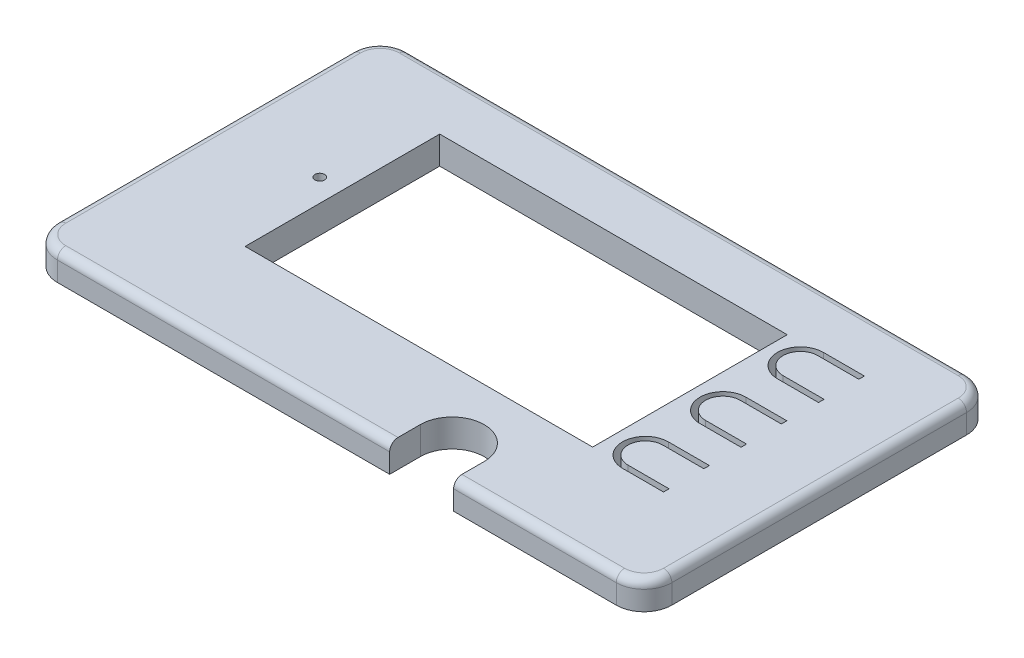
SolidWorks part; units mm, degrees
ref_plane "Front Plane" through (0, 0, 0) normal (0, 0, 1) x (1, 0, 0)
ref_plane "Top Plane" through (0, 0, 0) normal (0, 1, 0) x (1, 0, 0)
ref_plane "Right Plane" through (0, 0, 0) normal (1, 0, 0) x (0, 0, -1)
sketch "Sketch1" plane through (0, 0, 0) normal (0, 1, 0) x (1, 0, 0)
  line L1 (-28.067, -16.002) -> (28.067, -16.002)
  line L2 (-28.067, -16.002) -> (-28.067, 16.002)
  line L3 (-28.067, 16.002) -> (28.067, 16.002)
  line L4 (28.067, -16.002) -> (28.067, 16.002)
  line L5 (-28.067, -16.002) -> (28.067, 16.002) construction
  line L6 (-28.067, 16.002) -> (28.067, -16.002) construction
  point P0 (0, 0)
  dimension "D1" = 56.134
  dimension "D2" = 32.004
extrude "Boss-Extrude1" add sketch "Sketch1" along normal blind 2.54
sketch "Sketch2" plane through (0, 2.54, 0) normal (0, 1, 0) x (1, 0, 0)
  line L0 (28.067, -16.002) -> (28.067, 16.002) construction
  line L1 (14.478, -7.112) -> (-17.272, -7.112)
  line L2 (14.478, -7.112) -> (14.478, 10.668)
  line L3 (14.478, 10.668) -> (-17.272, 10.668)
  line L4 (-17.272, -7.112) -> (-17.272, 10.668)
  line L5 (14.478, -7.112) -> (-17.272, 10.668) construction
  line L6 (14.478, 10.668) -> (-17.272, -7.112) construction
  line L9 (28.067, 16.002) -> (-28.067, 16.002) construction
  point P0 (-1.397, 1.778)
  point P6 (1.7092, -3.8207)
  dimension "D1" = 13.589
  dimension "D2" = 17.78
  dimension "D3" = 31.75
  dimension "D4" = 5.334
extrude "Cut-Extrude1" cut sketch "Sketch2" against normal up to surface (2.54 mm away) up to face at (0, 0, 0)
fillet "Fillet1" radius 2.54 4 edges at (-28.067, 1.27, -16.002) (28.067, 1.27, -16.002) (28.067, 1.27, 16.002) (-28.067, 1.27, 16.002)
sketch "Sketch3" plane through (0, 0, 0) normal (0, -1, 0) x (1, 0, 0)
  line L1 (28.067, 13.462) -> (28.067, -13.462) construction
  line L2 (25.527, -16.002) -> (-25.527, -16.002) construction
  circle A0 centre (22.7076, 7.112) radius 1.016
  circle A1 centre (22.7076, -10.668) radius 1.016
  dimension "D1" = 2.032
  dimension "D2" = 17.78
  dimension "D3" = 5.334
  dimension "D4" = 5.3594
extrude "Boss-Extrude2" add sketch "Sketch3" along normal blind 3.81
fillet "Fillet2" radius 0.762 8 edges at (-27.3231, 2.54, 15.2581) (-28.067, 2.54, 0) (-27.3231, 2.54, -15.2581) (0, 2.54, -16.002) (27.3231, 2.54, -15.2581) (28.067, 2.54, 0) (27.3231, 2.54, 15.2581) (0, 2.54, 16.002)
sketch "Sketch4" plane through (0, 2.54, 0) normal (0, 1, 0) x (1, 0, 0)
  line L0 (28.067, 13.462) -> (28.067, -13.462) construction
  line L1 (25.527, -16.002) -> (-25.527, -16.002) construction
  line L2 (4.826, -13.208) -> (4.826, -16.002)
  line L3 (10.668, -13.208) -> (10.668, -16.002)
  line L4 (10.668, -16.002) -> (4.826, -16.002)
  arc A1 (10.668, -13.208) -> (4.826, -13.208) centre (7.747, -13.208) ccw
  dimension "D2" = 5.842
  dimension "D1" = 20.32
  dimension "D3" = 2.794
extrude "Cut-Extrude2" cut sketch "Sketch4" against normal up to surface (2.54 mm away) up to face at (22.7076, 0, -11.684)
sketch "Sketch5" plane through (0, 2.54, 0) normal (0, 1, 0) x (1, 0, 0)
  line L0 (17.526, 10.414) -> (21.2725, 10.414)
  line L1 (21.2725, 7.239) -> (17.526, 7.239)
  line L2 (17.526, 10.922) -> (21.2725, 10.922)
  line L3 (21.2725, 6.731) -> (17.526, 6.731)
  line L6 (21.2725, 8.8265) -> (15.547, 8.8265) construction
  line L7 (21.2725, 10.922) -> (21.2725, 10.414)
  line L8 (21.2725, 7.239) -> (21.2725, 6.731)
  line L9 (14.478, 10.668) -> (-17.272, 10.668) construction
  line L11 (14.478, -7.112) -> (14.478, 10.668) construction
  arc A2 (21.2725, 10.414) -> (21.2725, 7.239) centre (21.2725, 8.8265) cw construction
  arc A3 (21.2725, 10.922) -> (21.2725, 6.731) centre (21.2725, 8.8265) cw construction
  arc A4 (17.526, 10.922) -> (17.526, 6.731) centre (17.526, 8.8265) ccw
  arc A5 (17.526, 7.239) -> (17.526, 10.414) centre (17.526, 8.8265) cw
  point P14 (14.7975, 10.4943)
  point P15 (0, 0)
  point P16 (21.389, 12.6817)
  point P17 (16.8866, 12.6997)
  point P18 (16.7605, 8.5087)
  point P20 (21.389, 10.922)
  point P21 (17.7066, 10.414)
  point P22 (18.8057, 10.414)
  point P23 (0, 0)
  point P24 (15.4305, 8.8265)
  dimension "D3" = 5.842
  dimension "D5" = 3.048
  dimension "D2" = 3.175
  dimension "D4" = 0.254
  dimension "D1" = 0.508
extrude "Cut-Extrude3" cut sketch "Sketch5" against normal up to surface (2.54 mm away) up to face at (2.5823, 0, 4.6249)
sketch "Sketch8" plane through (0, 0, 0) normal (0, -1, 0) x (1, 0, 0)
  line L0 (21.2725, -10.922) -> (17.526, -10.922) construction
  line L1 (21.2725, -6.731) -> (20.0025, -6.731)
  line L2 (21.2725, -6.731) -> (21.2725, -10.922)
  line L3 (21.2725, -10.922) -> (20.0025, -10.922)
  line L4 (20.0025, -6.731) -> (20.0025, -10.922)
  dimension "D1" = 1.27
extrude "Cut-Extrude5" cut sketch "Sketch8" against normal blind 1.27
pattern_linear "LPattern1" count 3 spacing 7.0802 along (0, 0, 1) of "Cut-Extrude3", "Cut-Extrude5"
sketch "Sketch9" plane through (0, 2.54, 0) normal (0, 1, 0) x (1, 0, 0)
  line L0 (14.478, 10.668) -> (-17.272, 10.668) construction
  circle A0 centre (-19.3379, 1.778) radius 0.4445
  dimension "D2" = 0.889
  dimension "D1" = 8.89
extrude "Cut-Extrude6" cut sketch "Sketch9" against normal up to surface (2.54 mm away) up to face at (18.8754, 0, -1.7462)
